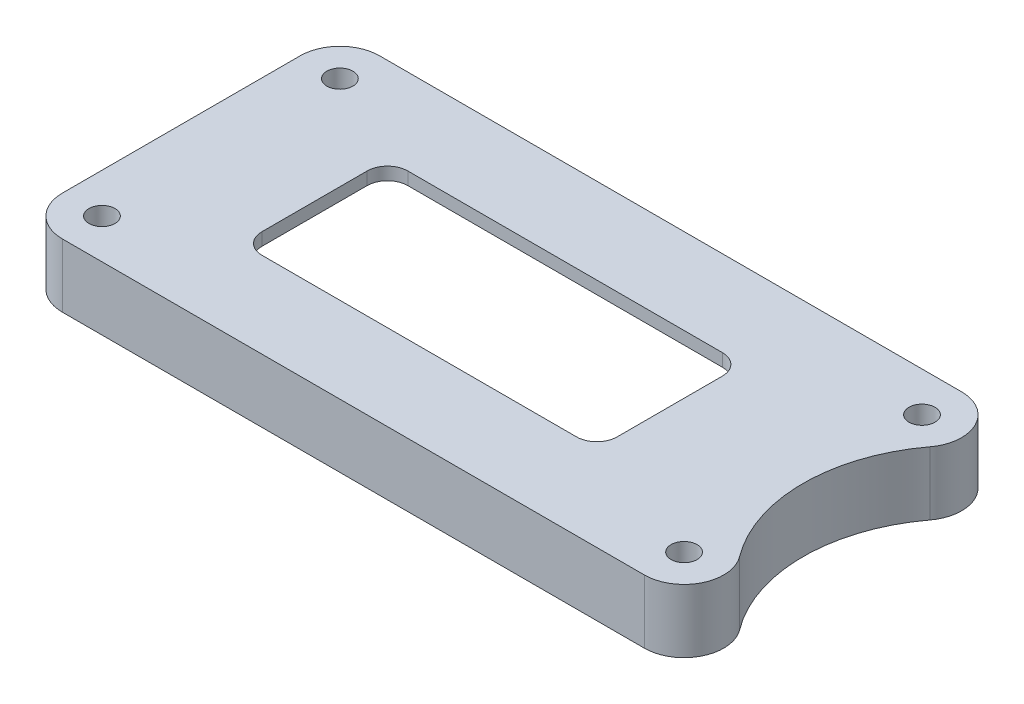
SolidWorks part; units mm, degrees
ref_plane "Front Plane" through (0, 0, 0) normal (0, 0, 1) x (1, 0, 0)
ref_plane "Top Plane" through (0, 0, 0) normal (0, 1, 0) x (1, 0, 0)
ref_plane "Right Plane" through (0, 0, 0) normal (1, 0, 0) x (0, 0, -1)
sketch "Sketch1" plane through (0, 0, 0) normal (0, 1, 0) x (1, 0, 0)
  line L1 (-22.5, 12.5) -> (22.5, 12.5)
  line L2 (-22.5, 12.5) -> (-22.5, -12.5)
  line L3 (-22.5, -12.5) -> (22.5, -12.5)
  line L4 (22.5, 12.5) -> (22.5, -12.5)
  line L5 (-22.5, 12.5) -> (22.5, -12.5) construction
  line L6 (-22.5, -12.5) -> (22.5, 12.5) construction
  point P0 (0, 0)
  dimension "D1" = 25
  dimension "D2" = 45
extrude "Boss-Extrude1" add sketch "Sketch1" along normal blind 5
sketch "Sketch2" plane through (0, 5, 0) normal (0, 1, 0) x (1, 0, 0)
  line L1 (-14, -5.75) -> (14, -5.75)
  line L2 (-14, -5.75) -> (-14, 5.75)
  line L3 (-14, 5.75) -> (14, 5.75)
  line L4 (14, -5.75) -> (14, 5.75)
  line L5 (-14, -5.75) -> (14, 5.75) construction
  line L6 (-14, 5.75) -> (14, -5.75) construction
  point P0 (0, 0)
  dimension "D1" = 28
  dimension "D2" = 11.5
extrude "Cut-Extrude1" cut sketch "Sketch2" against normal through all
shell "Shell1" thickness 1 removed face at (14, 2.5, 0) removed face at (0, 2.5, 5.75) removed face at (-14, 2.5, 0) removed face at (0, 2.5, -5.75) removed face at (0, 0, 0)
fillet "Fillet1" radius 1.6 4 edges at (-14, 4.5, -5.75) (14, 4.5, -5.75) (14, 4.5, 5.75) (-14, 4.5, 5.75)
sketch "Sketch3" plane through (0, 4, 0) normal (0, -1, 0) x (1, 0, 0)
  line L4 (21.5, -11.5) -> (21.5, 11.5)
  line L5 (21.5, 11.5) -> (-21.5, 11.5)
  line L6 (-21.5, 11.5) -> (-21.5, -11.5)
  line L7 (-21.5, -11.5) -> (21.5, -11.5)
  line L8 (21.5, -11.5) -> (21.5, 11.5)
  line L9 (21.5, 11.5) -> (-21.5, 11.5)
  line L10 (-21.5, 11.5) -> (-21.5, -11.5)
  line L11 (-21.5, -11.5) -> (21.5, -11.5)
  circle A0 centre (-12.9353, 8.721) radius 1.25 construction
  circle A1 centre (17.0647, 8.721) radius 1.25 construction
  circle A2 centre (17.0647, -7.779) radius 1.25 construction
  circle A3 centre (-12.9353, -7.779) radius 1.25 construction
  circle A4 centre (-12.9353, 8.721) radius 1.25
  circle A5 centre (17.0647, 8.721) radius 1.25
  circle A6 centre (17.0647, -7.779) radius 1.25
  circle A7 centre (-12.9353, -7.779) radius 1.25
  dimension "D1" = 0
fillet "Fillet2" radius 3.125 4 edges at (-21.5, 2, 11.5) (-21.5, 2, -11.5) (21.5, 2, 11.5) (21.5, 2, -11.5)
sketch "Sketch4" plane through (0, 0, 0) normal (0, -1, 0) x (1, 0, 0)
  line L0 (22.5, -12.5) -> (37, -12.5)
  line L1 (22.5, 12.5) -> (40, 12.5)
  line L2 (-22.5, -12.5) -> (-27.5, -12.5)
  line L3 (-22.5, 12.5) -> (-27.5, 12.5)
  line L4 (22.5, -12.5) -> (22.5, 12.5)
  line L5 (22.5, 12.5) -> (-22.5, 12.5)
  line L6 (-22.5, 12.5) -> (-22.5, -12.5)
  line L7 (-22.5, -12.5) -> (22.5, -12.5)
  line L8 (22.5, -12.5) -> (22.5, 12.5)
  line L9 (22.5, 12.5) -> (-22.5, 12.5)
  line L10 (-22.5, 12.5) -> (-22.5, -12.5)
  line L11 (-22.5, -12.5) -> (22.5, -12.5)
  circle A0 centre (37, 0) radius 12.5
  circle A1 centre (-27.5, 0) radius 12.5
  line M15 (22.5, -12.5) -> (22.5, 12.5)
  dimension "D2" = 25
  dimension "D4" = 25
  dimension "D3" = 14.5
  dimension "D5" = 5
  dimension "D1" = 0
extrude "Boss-Extrude2" add sketch "Sketch4" against normal up to surface (5 mm away) contours A0 L1 L0 M15 region at (22.789, 0, 0) up to face at (0, 5, 0)
fillet "Fillet3" radius 3.125 2 edges at (37, 2.5, -12.5) (37, 2.5, 12.5)
fillet "Fillet4" radius 3.125 2 edges at (-22.5, 2.5, -12.5) (-22.5, 2.5, 12.5)
sketch "Sketch6" plane through (0, 0, 0) normal (0, -1, 0) x (1, 0, 0)
  line L1 (-22.5, -12.5) -> (-24.5, -12.5)
  line L2 (-22.5, -12.5) -> (-22.5, 12.5)
  line L3 (-22.5, 9.375) -> (-22.5, -9.375)
  line L4 (-19.375, -12.5) -> (24.5, -12.5)
  line L5 (24.5, 12.5) -> (-19.375, 12.5)
  line L6 (-22.5, 9.375) -> (-22.5, -9.375)
  line L7 (-19.375, -12.5) -> (24.5, -12.5)
  line L8 (24.5, 12.5) -> (-19.375, 12.5)
  line L9 (-22.5, 12.5) -> (-24.5, 12.5)
  line L10 (-22.5, -12.5) -> (22.5, -12.5)
  line L11 (22.5, -12.5) -> (22.5, 12.5)
  line L12 (22.5, 12.5) -> (-22.5, 12.5)
  line L13 (-22.5, 12.5) -> (-22.5, -12.5)
  line L14 (-22.5, -12.5) -> (22.5, -12.5)
  line L15 (22.5, -12.5) -> (22.5, 12.5)
  line L16 (22.5, 12.5) -> (-22.5, 12.5)
  line L17 (-22.5, 12.5) -> (-22.5, -12.5)
  line L18 (-24.5, -12.5) -> (-24.5, 12.5)
  line L19 (-22.5, -12.5) -> (-18.375, -12.5)
  line L20 (-22.5, -12.5) -> (-22.5, 12.5)
  line L21 (-22.5, 12.5) -> (-18.375, 12.5)
  line L22 (-18.375, -12.5) -> (-18.375, 12.5)
  arc A6 (-22.5, -9.375) -> (-19.375, -12.5) centre (-19.375, -9.375) ccw
  arc A7 (24.5, -12.5) -> (27, -7.5) centre (24.5, -9.375) ccw
  arc A8 (27, 7.5) -> (27, -7.5) centre (37, 0) ccw
  arc A9 (27, 7.5) -> (24.5, 12.5) centre (24.5, 9.375) ccw
  arc A10 (-19.375, 12.5) -> (-22.5, 9.375) centre (-19.375, 9.375) ccw
  arc A11 (-22.5, -9.375) -> (-19.375, -12.5) centre (-19.375, -9.375) ccw
  arc A12 (24.5, -12.5) -> (27, -7.5) centre (24.5, -9.375) ccw
  arc A13 (27, 7.5) -> (27, -7.5) centre (37, 0) ccw
  arc A14 (27, 7.5) -> (24.5, 12.5) centre (24.5, 9.375) ccw
  arc A15 (-19.375, 12.5) -> (-22.5, 9.375) centre (-19.375, 9.375) ccw
  line M15 (-21.5, -8.375) -> (-21.5, 8.375)
  arc M16 (-21.5, 8.375) -> (-18.375, 11.5) centre (-18.375, 8.375) cw
  arc M22 (-18.375, -11.5) -> (-21.5, -8.375) centre (-18.375, -8.375) cw
  line M23 (-22.5, 9.375) -> (-22.5, -9.375)
  arc M24 (-22.5, -9.375) -> (-19.375, -12.5) centre (-19.375, -9.375) ccw
  line M25 (-19.375, -12.5) -> (24.5, -12.5)
  arc M30 (-19.375, 12.5) -> (-22.5, 9.375) centre (-19.375, 9.375) ccw
  dimension "D3" = 2
  dimension "D1" = 0
  dimension "D2" = 0
extrude "Boss-Extrude3" add sketch "Sketch6" against normal up to surface (5 mm away) contours L22 M22 M16 M15 | L18 L1 L2 L9 M23 | L22 L16 M25 M22 M15 M16 M30 M23 M24 | L2 L14 M24 | L16 L2 M30 region at (-23.5, 0, 0) region at (-21.802, 0, -11.802) region at (-22.2466, 0, 0) region at (-21.802, 0, 11.802) region at (-19.884, 0, 0) up to face at (0, 5, 0)
fillet "Fillet5" radius 3.125 4 edges at (-24.5, 2.5, -12.5) (-24.5, 2.5, 12.5) (-18.375, 2, 11.5) (-18.375, 2, -11.5)
sketch "Sketch7" plane through (0, 0, 0) normal (0, -1, 0) x (-1, 0, 0)
  line L0 (-2.75, 0) -> (2.75, 0) construction
  circle A0 centre (-24.5, 9.375) radius 1.025
  circle A1 centre (-24.5, -9.375) radius 1.025
  circle A2 centre (21.375, 9.375) radius 1.025
  circle A3 centre (21.375, -9.375) radius 1.025
  dimension "D1" = 2.05
  dimension "D2" = 2.05
extrude "Cut-Extrude2" cut sketch "Sketch7" against normal through all contours A0 | A1 | A3 | A2 region at (24.5, 0, -9.375) region at (24.5, 0, 9.375) region at (-21.375, 0, -9.375) region at (-21.375, 0, 9.375)
ref_point "Point1"
